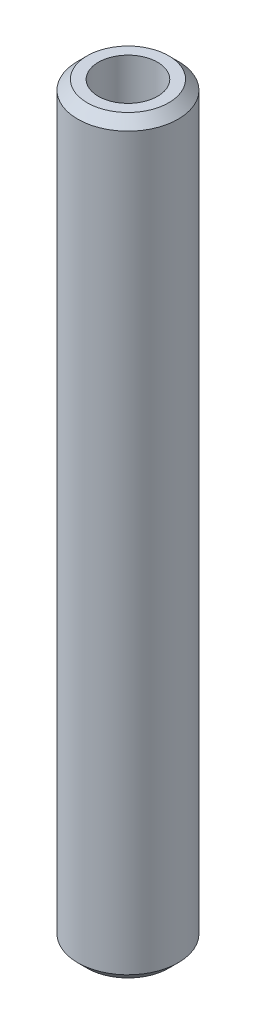
SolidWorks part; units mm, degrees
ref_plane "Front Plane" through (0, 0, 0) normal (0, 0, 1) x (1, 0, 0)
ref_plane "Top Plane" through (0, 0, 0) normal (0, 1, 0) x (1, 0, 0)
ref_plane "Right Plane" through (0, 0, 0) normal (1, 0, 0) x (0, 0, -1)
sketch "Sketch1" plane through (0, 0, 0) normal (0, 1, 0) x (1, 0, 0)
  circle A0 centre (0, 0) radius 12.5
  dimension "SHAFT_OD" = 25
extrude "Boss-Extrude1" add sketch "Sketch1" along normal blind 186.5923
sketch "Sketch2" plane through (0, 0, 0) normal (0, 1, 0) x (1, 0, 0)
  circle A0 centre (0, 0) radius 7.3644
  dimension "BORE_D" = 14.7287
extrude "Cut-Extrude1" cut sketch "Sketch2" along normal through all
chamfer "Chamfer1" distance 2.3573 angle 45 2 edges at (0, 186.5923, 12.5) (0, 0, 12.5)
